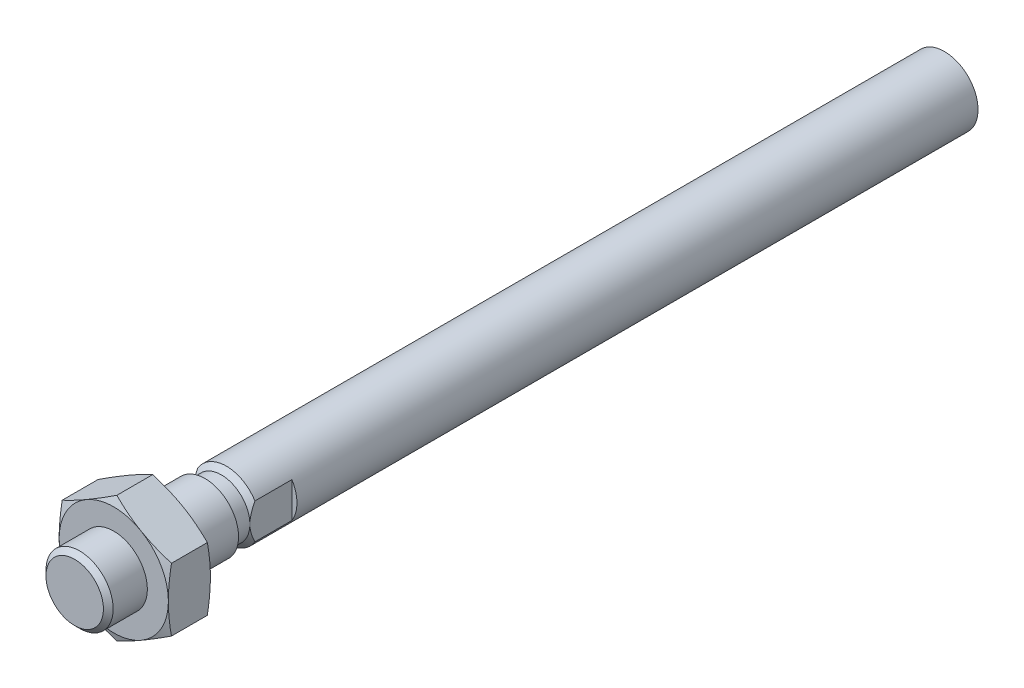
SolidWorks part; units mm, degrees
ref_plane "前视基准面" through (0, 0, 0) normal (0, 0, 1) x (1, 0, 0)
ref_plane "上视基准面" through (0, 0, 0) normal (0, 1, 0) x (1, 0, 0)
ref_plane "右视基准面" through (0, 0, 0) normal (1, 0, 0) x (0, 0, -1)
sketch "草图1" plane through (0, 0, 0) normal (1, 0, 0) x (0, 0, -1)
  line L0 (-38.5, 0) -> (38.5, 0) construction
  line L1 (0, 0) -> (0, 12.5) construction
  line L2 (0, 12.5) -> (15, 12.5) construction
  line L3 (15, 12.5) -> (77, 12.5) construction
  line L4 (51.5, 10) -> (51.5, -10) construction
  line L5 (-38.5, 0) -> (-52.5, 0) construction
  line L6 (-52.5, 10) -> (-52.5, -10) construction
  line L7 (-52.5, 0) -> (-79.5, 0) construction
  line L8 (38.5, 0) -> (59.5, 0) construction
  line L9 (59.5, 10) -> (59.5, -10) construction
  line L10 (-79.5, 4) -> (-79.5, -4) construction
  circle A0 centre (-31, 0) radius 4.864
  circle A1 centre (50.5, 0) radius 4
  point P6 (-24, 0)
  point P8 (24, 0)
  point P9 (-31, 0)
  point P10 (31, 0)
  point P13 (51.5, 0)
  point P16 (-49.7, 0)
  point P18 (-41.7, 0)
  point P21 (-52.5, 4)
  point P22 (-64, 0)
  point P24 (-62.05, 0)
  point P25 (-57.05, 0)
  point P26 (-74.85, 0)
  point P27 (-69.85, 0)
  point P28 (50.5, 0)
  dimension "D2" = 2.8
  dimension "X" = 9.728
  dimension "P1" = 8
  dimension "D1" = 77
  dimension "行程" = 15
  dimension "A" = 62
  dimension "S" = 25
  dimension "F" = 14.5
  dimension "G1" = 7.5
  dimension "D1用" = 13
  dimension "L" = 20
  dimension "B" = 14
  dimension "M" = 8
  dimension "D3" = 1.95
  dimension "V" = 8
  dimension "C" = 27
  dimension "H" = 15.5
  dimension "D4" = 4.65
  dimension "E" = 5
  dimension "J" = 5
  dimension "D" = 21
  dimension "G" = 12
  dimension "L1" = 20
  dimension "K" = 8
sketch "草图2" plane through (0, 0, 0) normal (0, 0, 1) x (1, 0, 0)
  line L0 (-6, 0) -> (6, 0) construction
  line L1 (0, 15.0111) -> (-13, 7.5056)
  line L2 (-13, 7.5056) -> (-13, -7.5056)
  line L3 (-13, -7.5056) -> (0, -15.0111)
  line L4 (0, -15.0111) -> (13, -7.5056)
  line L5 (13, -7.5056) -> (13, 7.5056)
  line L6 (13, 7.5056) -> (0, 15.0111)
  line L7 (0, 7.5056) -> (-6.5, 3.7528)
  line L8 (-6.5, 3.7528) -> (-6.5, -3.7528)
  line L9 (-6.5, -3.7528) -> (0, -7.5056)
  line L10 (0, -7.5056) -> (6.5, -3.7528)
  line L11 (6.5, -3.7528) -> (6.5, 3.7528)
  line L12 (6.5, 3.7528) -> (0, 7.5056)
  line L13 (0, 0) -> (0, 4) construction
  circle A0 centre (0, 0) radius 13 construction
  circle A1 centre (0, 0) radius 6.5 construction
  circle A2 centre (0, 0) radius 14.5 construction
  dimension "T1" = 26
  dimension "T" = 13
  dimension "P" = 29
  dimension "Q" = 12
sketch "行程" plane through (0, 0, 0) normal (1, 0, 0) x (0, 0, -1)
  line L0 (24, 0) -> (9, 0)
  line L1 (-38.5, 0) -> (38.5, 0) construction
  dimension "D1" = 15
sketch "草图4" plane through (0, 0, 0) normal (0, 0, 1) x (1, 0, 0)
  circle A0 centre (0, 0) radius 4
extrude "凸台-拉伸1" add sketch "草图4" against normal up to vertex (-64 mm away) from vertex up to point (0, 0, 64) starting at point (0, 0, 79.5)
cosmetic thread "装饰螺纹线1" parameters "D2"=6.8
cosmetic thread "装饰螺纹线2" parameters "D2"=6.8
sketch "草图5" plane through (0, 0, 64) normal (0, 0, -1) x (-1, 0, 0)
  circle A0 centre (0, 0) radius 3.4
  dimension "D1" = 6.8
extrude "凸台-拉伸2" add sketch "草图5" along normal up to vertex (1.95 mm away) up to point (0, 0, 62.05)
sketch "草图6" plane through (0, 0, 62.05) normal (0, 0, -1) x (-1, 0, 0)
  circle A0 centre (0, 0) radius 4
extrude "凸台-拉伸3" add sketch "草图6" along normal up to vertex (86.05 mm away) up to point (0, 0, -24)
sketch "草图7" plane through (0, 0, 0) normal (0, 0, 1) x (1, 0, 0)
  line L0 (6.5, -3.7528) -> (6.5, 3.7528) construction
  line L1 (6.5, 3.7528) -> (0, 7.5056) construction
  line L2 (0, 7.5056) -> (-6.5, 3.7528) construction
  line L3 (-6.5, 3.7528) -> (-6.5, -3.7528) construction
  line L4 (-6.5, -3.7528) -> (0, -7.5056) construction
  line L5 (0, -7.5056) -> (6.5, -3.7528) construction
  line L6 (6.5, -3.7528) -> (6.5, 3.7528)
  line L7 (6.5, 3.7528) -> (0, 7.5056)
  line L8 (0, 7.5056) -> (-6.5, 3.7528)
  line L9 (-6.5, 3.7528) -> (-6.5, -3.7528)
  line L10 (-6.5, -3.7528) -> (0, -7.5056)
  line L11 (0, -7.5056) -> (6.5, -3.7528)
extrude "凸台-拉伸4" add sketch "草图7" against normal up to vertex (-69.85 mm away) from vertex up to point (0, 0, 69.85) starting at point (0, 0, 74.85)
sketch "草图8" plane through (0, 0, 0) normal (0, 1, 0) x (1, 0, 0)
  line L0 (-6.5, -74.85) -> (-15.3687, -74.85)
  line L1 (-6.5, -74.85) -> (-13.3687, -72.35)
  line L2 (-6.5, -72.35) -> (0, -72.35) construction
  line L3 (-6.5, -69.85) -> (-6.5, -74.85) construction
  line L4 (0, -52.5) -> (0, -79.5) construction
  line L5 (-6.5, -69.85) -> (-13.3687, -72.35)
  line L6 (-6.5, -69.85) -> (-15.3687, -69.85)
  line L7 (-15.3687, -69.85) -> (-15.3687, -74.85)
  dimension "D1" = 20
  dimension "D2" = 2
revolve "切除-旋转1" cut sketch "草图8" angle 360 mid plane about L7
chamfer "倒角1" distance 0.58 angle 45 1 edges at (4, 0, 79.5)
chamfer "倒角2" distance 0.6 angle 45 1 edges at (-4, 0, 62.05)
sketch "草图9" plane through (0, 0, 0) normal (0, 0, 1) x (1, 0, 0)
  line L0 (-3.4, 7.5056) -> (-3.4, -7.5056)
  line L1 (3.4, 7.5056) -> (3.4, -7.5056)
  line L2 (-3.4, 7.5056) -> (3.4, 7.5056)
  line L3 (-3.4, -7.5056) -> (3.4, -7.5056)
  circle A0 centre (0, 0) radius 3.4 construction
extrude "切除-拉伸1" cut sketch "草图9" along normal up to vertex (62.05 mm away) from vertex flip side to cut up to point (0, 0, 62.05) starting at point (0, 0, 57.05)
